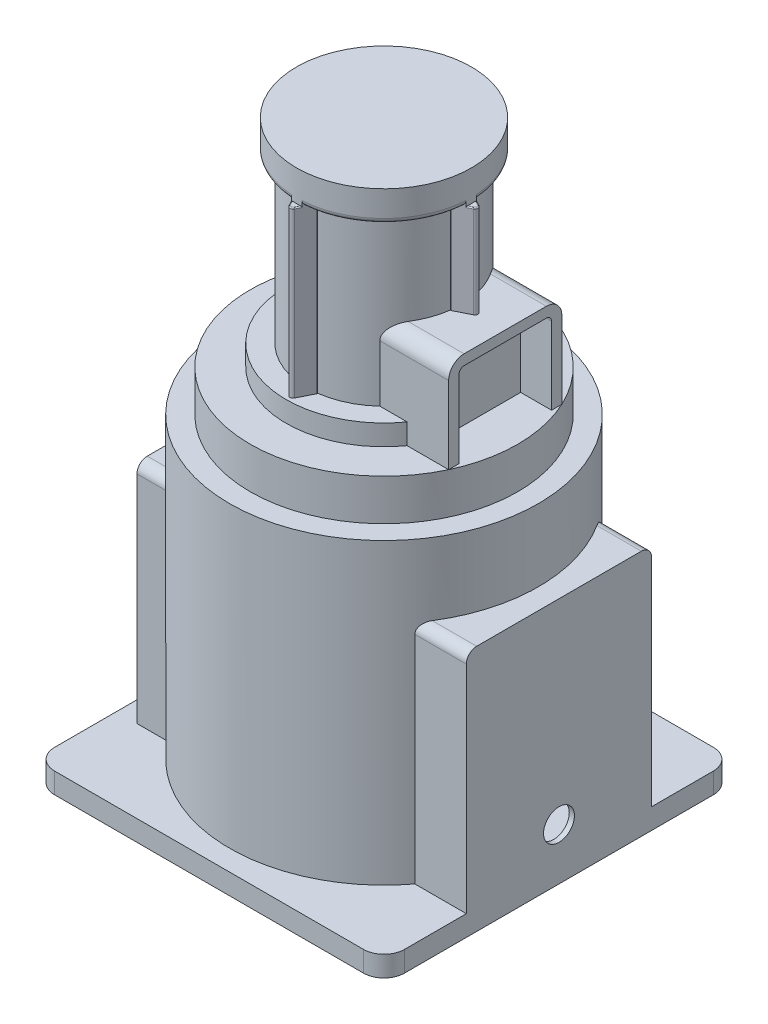
SolidWorks part; units mm, degrees
material "201 Annealed Stainless Steel (SS)"
ref_plane "Front Plane" through (0, 0, 0) normal (0, 0, 1) x (1, 0, 0)
ref_plane "Top Plane" through (0, 0, 0) normal (0, 1, 0) x (1, 0, 0)
ref_plane "Right Plane" through (0, 0, 0) normal (1, 0, 0) x (0, 0, -1)
sketch "Sketch1" plane through (0, 0, 0) normal (0, 1, 0) x (1, 0, 0)
  line L1 (150, -170) -> (-150, -170)
  line L2 (170, -150) -> (170, 150)
  line L3 (150, 170) -> (-150, 170)
  line L4 (-170, -150) -> (-170, 150)
  line L5 (170, -170) -> (-170, 170) construction
  line L6 (170, 170) -> (-170, -170) construction
  arc A0 (170, -150) -> (150, -170) centre (150, -150) cw
  arc A1 (-170, -150) -> (-150, -170) centre (-150, -150) ccw
  arc A2 (150, 170) -> (170, 150) centre (150, 150) cw
  arc A3 (-150, 170) -> (-170, 150) centre (-150, 150) ccw
  point P0 (0, 0)
  dimension "D3" = 20
  dimension "D1" = 340
  dimension "D2" = 340
extrude "Boss-Extrude1" add sketch "Sketch1" along normal blind 20
sketch "Sketch2" plane through (0, 20, 0) normal (0, 1, 0) x (1, 0, 0)
  line L4 (170, -150) -> (170, 150)
  line L5 (150, 170) -> (-150, 170)
  line L6 (-170, 150) -> (-170, -150)
  line L7 (-150, -170) -> (150, -170)
  line L8 (170, -150) -> (170, 150)
  line L9 (150, 170) -> (-150, 170)
  line L10 (-170, 150) -> (-170, -150)
  line L11 (-150, -170) -> (150, -170)
  line L12 (-150, 0) -> (-150, -90)
  line L13 (-150, -90) -> (-120, -90)
  line L14 (120, -90) -> (150, -90)
  line L15 (0, 0) -> (-150, 0) construction
  line L16 (150, -150) -> (150, 150)
  line L17 (150, 150) -> (-150, 150)
  line L18 (-150, 150) -> (-150, -150)
  line L19 (-150, -150) -> (150, -150)
  line L20 (150, -150) -> (150, 150)
  line L21 (150, 150) -> (-150, 150)
  line L22 (-150, 150) -> (-150, -150)
  line L23 (-150, -150) -> (150, -150)
  line L24 (150, -90) -> (170, -90)
  line L25 (150, 90) -> (170, 90)
  line L26 (120, 90) -> (150, 90)
  line L27 (-150, 90) -> (-120, 90)
  arc A4 (150, -170) -> (170, -150) centre (150, -150) ccw
  arc A5 (170, 150) -> (150, 170) centre (150, 150) ccw
  arc A6 (-150, 170) -> (-170, 150) centre (-150, 150) ccw
  arc A7 (-170, -150) -> (-150, -170) centre (-150, -150) ccw
  arc A8 (150, -170) -> (170, -150) centre (150, -150) ccw
  arc A9 (170, 150) -> (150, 170) centre (150, 150) ccw
  arc A10 (-150, 170) -> (-170, 150) centre (-150, 150) ccw
  arc A11 (-170, -150) -> (-150, -170) centre (-150, -150) ccw
  circle A12 centre (0, 0) radius 150
  dimension "D3" = 30
  dimension "D1" = 0
  dimension "D2" = 20
extrude "Boss-Extrude2" add sketch "Sketch2" along normal blind 220 contours A12 | A12 L12 L13 | A12 L14 L20 | L25 L20 L24 L8 | A12 L20 L26 | A12 L27 L22 region at (160, 20, 0) region at (141.1785, 20, 67.9748) region at (141.1785, 20, -67.9748) region at (0, 20, 0) region at (-141.1785, 20, 67.9748) region at (-141.1785, 20, -67.9748)
sketch "Sketch3" plane through (0, 240, 0) normal (0, 1, 0) x (1, 0, 0)
  line L6 (170, -90) -> (170, 90)
  line L7 (170, 90) -> (120, 90)
  line L8 (-120, 90) -> (-150, 90)
  line L9 (-150, 90) -> (-150, -90)
  line L10 (-150, -90) -> (-120, -90)
  line L11 (120, -90) -> (170, -90)
  line L12 (170, -90) -> (170, 90)
  line L13 (170, 90) -> (120, 90)
  line L14 (-120, 90) -> (-150, 90)
  line L15 (-150, 90) -> (-150, -90)
  line L16 (-150, -90) -> (-120, -90)
  line L17 (120, -90) -> (170, -90)
  circle A0 centre (0, 0) radius 150
  arc A2 (120, 90) -> (-120, 90) centre (0, 0) ccw
  arc A3 (-120, -90) -> (120, -90) centre (0, 0) ccw
  arc A4 (120, 90) -> (-120, 90) centre (0, 0) ccw
  arc A5 (-120, -90) -> (120, -90) centre (0, 0) ccw
  arc M11 (120, 90) -> (-120, 90) centre (0, 0) ccw
  arc M15 (-120, -90) -> (120, -90) centre (0, 0) ccw
  dimension "D1" = 0
extrude "Boss-Extrude3" add sketch "Sketch3" along normal blind 70 contours A0 M15 M11 region at (0, 240, 0)
sketch "Sketch4" plane through (0, 310, 0) normal (0, 1, 0) x (1, 0, 0)
  circle A1 centre (0, 0) radius 150
  circle A2 centre (0, 0) radius 150
  circle A4 centre (0, 0) radius 130
  circle A5 centre (0, 0) radius 130
  dimension "D1" = 0
  dimension "D2" = 20
extrude "Boss-Extrude4" add sketch "Sketch4" along normal blind 40 contours A5 region at (0, 310, 0)
sketch "Sketch5" plane through (0, 350, 0) normal (0, 1, 0) x (1, 0, 0)
  circle A1 centre (0, 0) radius 130
  circle A2 centre (0, 0) radius 130
  circle A4 centre (0, 0) radius 95
  circle A5 centre (0, 0) radius 95
  dimension "D1" = 0
  dimension "D2" = 35
extrude "Boss-Extrude5" add sketch "Sketch5" along normal blind 20 contours A5 region at (0, 350, 0)
sketch "Sketch6" plane through (0, 350, 0) normal (0, 1, 0) x (1, 0, 0)
  line L0 (0, 0) -> (0, -130) construction
  line L1 (0, 0) -> (0, -55)
  line L2 (0, -55) -> (117.7922, -55)
  line L3 (0, 0) -> (130, 0) construction
  line L4 (0, 55) -> (117.7922, 55)
  line L5 (0, 0) -> (0, 55)
  line L6 (117.7922, 55) -> (117.7922, -55)
  circle A1 centre (0, 0) radius 130
  circle A2 centre (0, 0) radius 130
  circle M5 centre (0, 0) radius 95
  dimension "D2" = 55
  dimension "D1" = 0
extrude "Boss-Extrude6" add sketch "Sketch6" along normal blind 90 contours L5 L1 L2 L4 M5 | L6 L4 L2 M5 region at (44.8421, 350, 0) region at (103.1235, 350, 0)
sketch "Sketch7" plane through (0, 370, 0) normal (0, 1, 0) x (1, 0, 0)
  line L3 (77.4597, -55) -> (0, -55)
  line L4 (0, -55) -> (0, 55)
  line L5 (0, 55) -> (77.4597, 55)
  line L6 (77.4597, -55) -> (0, -55)
  line L7 (0, -55) -> (0, 55)
  line L8 (0, 55) -> (77.4597, 55)
  line L9 (0, 0) -> (-95, 0) construction
  line L10 (-75, 0) -> (-75, 10)
  line L11 (-75, 10) -> (-89.6334, 2.6833)
  line L12 (-20, -72.2842) -> (-20, 72.2842)
  line L13 (-20, -72.2842) -> (-20, 72.2842)
  line L14 (-75, 10) -> (-74.3421, 9.9123)
  line L15 (-75, -10) -> (-74.3421, -9.9123)
  line L16 (-75, -10) -> (-89.6334, -2.6833)
  line L17 (10, 75) -> (2.6833, 89.6334)
  line L18 (-10, 75) -> (-2.6833, 89.6334)
  line L19 (10, 75) -> (9.9123, 74.3421)
  line L20 (-10, 75) -> (-9.9123, 74.3421)
  line L21 (75, -10) -> (89.6334, -2.6833)
  line L22 (75, 10) -> (89.6334, 2.6833)
  line L23 (75, -10) -> (74.3421, -9.9123)
  line L24 (75, 10) -> (74.3421, 9.9123)
  line L25 (-10, -75) -> (-2.6833, -89.6334)
  line L26 (10, -75) -> (2.6833, -89.6334)
  line L27 (-10, -75) -> (-9.9123, -74.3421)
  line L28 (10, -75) -> (9.9123, -74.3421)
  arc A1 (77.4597, 55) -> (77.4597, -55) centre (0, 0) ccw
  arc A2 (77.4597, 55) -> (77.4597, -55) centre (0, 0) ccw
  circle A3 centre (0, 0) radius 75
  arc A4 (-20, 72.2842) -> (-20, -72.2842) centre (0, 0) ccw
  arc A5 (-20, 72.2842) -> (-20, -72.2842) centre (0, 0) ccw
  arc A6 (-89.6334, -2.6833) -> (-89.6334, 2.6833) centre (-88.2918, 0) cw
  arc A7 (-2.6833, 89.6334) -> (2.6833, 89.6334) centre (0, 88.2918) cw
  arc A8 (89.6334, 2.6833) -> (89.6334, -2.6833) centre (88.2918, 0) cw
  arc A9 (2.6833, -89.6334) -> (-2.6833, -89.6334) centre (0, -88.2918) cw
  line M9 (0, -55) -> (0, 55)
  line M10 (0, 55) -> (77.4597, 55)
  dimension "D1" = 0
  dimension "D2" = 20
extrude "Boss-Extrude7" add sketch "Sketch7" along normal blind 160 contours L13 L9 A3 | L9 L13 A3 | A3 L9 A6 L16 L15 | L9 L10 L11 A6 | A7 L18 L20 A3 L19 L17 | A8 L22 L24 A3 L23 L21 | A9 L26 L28 A3 L27 L25 | L9 L13 A3 L6 M9 | L9 L7 A3 L13 M10 | L6 A3 L7 M10 M9 region at (-0.4873, 370, 45.4129) region at (34.1514, 370, 0) region at (0, 370, 81.0778) region at (81.0778, 370, 0) region at (-81.2216, 370, -3.4408) region at (-81.0778, 370, 3.5311) region at (-0.4873, 370, -45.4129) region at (-42.8821, 370, -29.1938) region at (-42.8821, 370, 29.1938) region at (0, 370, -81.0778)
sketch "Sketch8" plane through (0, 530, 0) normal (0, 1, 0) x (1, 0, 0)
  line L16 (-75, 0) -> (-75, 10)
  line L17 (-75, 10) -> (-89.6334, 2.6833)
  line L18 (-89.6334, -2.6833) -> (-75, -10)
  line L19 (-75, -10) -> (-74.3421, -9.9123)
  line L20 (-9.9123, -74.3421) -> (-10, -75)
  line L21 (-10, -75) -> (-2.6833, -89.6334)
  line L22 (2.6833, -89.6334) -> (10, -75)
  line L23 (10, -75) -> (9.9123, -74.3421)
  line L24 (74.3421, -9.9123) -> (75, -10)
  line L25 (75, -10) -> (89.6334, -2.6833)
  line L26 (89.6334, 2.6833) -> (75, 10)
  line L27 (75, 10) -> (74.3421, 9.9123)
  line L28 (9.9123, 74.3421) -> (10, 75)
  line L29 (10, 75) -> (2.6833, 89.6334)
  line L30 (-2.6833, 89.6334) -> (-10, 75)
  line L31 (-10, 75) -> (-9.9123, 74.3421)
  line L32 (-75, 0) -> (-75, 10)
  line L33 (-75, 10) -> (-89.6334, 2.6833)
  line L34 (-89.6334, -2.6833) -> (-75, -10)
  line L35 (-75, -10) -> (-74.3421, -9.9123)
  line L36 (-9.9123, -74.3421) -> (-10, -75)
  line L37 (-10, -75) -> (-2.6833, -89.6334)
  line L38 (2.6833, -89.6334) -> (10, -75)
  line L39 (10, -75) -> (9.9123, -74.3421)
  line L40 (74.3421, -9.9123) -> (75, -10)
  line L41 (75, -10) -> (89.6334, -2.6833)
  line L42 (89.6334, 2.6833) -> (75, 10)
  line L43 (75, 10) -> (74.3421, 9.9123)
  line L44 (9.9123, 74.3421) -> (10, 75)
  line L45 (10, 75) -> (2.6833, 89.6334)
  line L46 (-2.6833, 89.6334) -> (-10, 75)
  line L47 (-10, 75) -> (-9.9123, 74.3421)
  arc A0 (-11.2339, 84.2544) -> (-85, 0) centre (0, 0) ccw
  circle A1 centre (0, 0) radius 85
  arc A8 (-9.9123, 74.3421) -> (-75, 0) centre (0, 0) ccw
  arc A9 (-89.6334, 2.6833) -> (-89.6334, -2.6833) centre (-88.2918, 0) ccw
  arc A10 (-74.3421, -9.9123) -> (-9.9123, -74.3421) centre (0, 0) ccw
  arc A11 (-2.6833, -89.6334) -> (2.6833, -89.6334) centre (0, -88.2918) ccw
  arc A12 (9.9123, -74.3421) -> (74.3421, -9.9123) centre (0, 0) ccw
  arc A13 (89.6334, -2.6833) -> (89.6334, 2.6833) centre (88.2918, 0) ccw
  arc A14 (74.3421, 9.9123) -> (9.9123, 74.3421) centre (0, 0) ccw
  arc A15 (2.6833, 89.6334) -> (-2.6833, 89.6334) centre (0, 88.2918) ccw
  arc A16 (-9.9123, 74.3421) -> (-75, 0) centre (0, 0) ccw
  arc A17 (-89.6334, 2.6833) -> (-89.6334, -2.6833) centre (-88.2918, 0) ccw
  arc A18 (-74.3421, -9.9123) -> (-9.9123, -74.3421) centre (0, 0) ccw
  arc A19 (-2.6833, -89.6334) -> (2.6833, -89.6334) centre (0, -88.2918) ccw
  arc A20 (9.9123, -74.3421) -> (74.3421, -9.9123) centre (0, 0) ccw
  arc A21 (89.6334, -2.6833) -> (89.6334, 2.6833) centre (88.2918, 0) ccw
  arc A22 (74.3421, 9.9123) -> (9.9123, 74.3421) centre (0, 0) ccw
  arc A23 (2.6833, 89.6334) -> (-2.6833, 89.6334) centre (0, 88.2918) ccw
  arc M25 (-9.9123, 74.3421) -> (-75, 0) centre (0, 0) ccw
  line M26 (-75, 0) -> (-75, 10)
  line M27 (-75, 10) -> (-89.6334, 2.6833)
  line M30 (-75, -10) -> (-74.3421, -9.9123)
  arc M31 (-74.3421, -9.9123) -> (-9.9123, -74.3421) centre (0, 0) ccw
  line M32 (-9.9123, -74.3421) -> (-10, -75)
  line M33 (-10, -75) -> (-2.6833, -89.6334)
  line M36 (10, -75) -> (9.9123, -74.3421)
  arc M37 (9.9123, -74.3421) -> (74.3421, -9.9123) centre (0, 0) ccw
  line M38 (74.3421, -9.9123) -> (75, -10)
  line M39 (75, -10) -> (89.6334, -2.6833)
  line M42 (75, 10) -> (74.3421, 9.9123)
  arc M43 (74.3421, 9.9123) -> (9.9123, 74.3421) centre (0, 0) ccw
  line M44 (9.9123, 74.3421) -> (10, 75)
  line M45 (10, 75) -> (2.6833, 89.6334)
  line M48 (-10, 75) -> (-9.9123, 74.3421)
  dimension "D1" = 0
  dimension "D2" = 10
extrude "Boss-Extrude8" add sketch "Sketch8" along normal blind 30 contours A1 L42 L46 A0 L34 L38 M39 M42 M43 M44 M45 M48 M25 M26 M27 M30 M31 M32 M33 M36 M37 M38 | A1 region at (0.009, 530, 0.0009)
fillet "Fillet1" radius 10 4 edges at (-135, 240, 90) (-135, 240, -90) (145, 240, -90) (145, 240, 90)
fillet "Fillet2" radius 15 2 edges at (84.3912, 440, -55) (84.3912, 440, 55)
fillet "Fillet3" radius 5 4 edges at (60.1041, 530, 60.1041) (60.1041, 530, -60.1041) (-60.1041, 530, -60.1041) (-60.1041, 530, 60.1041)
fillet "Fillet4" radius 1 12 edges at (-3.8796, 530, 87.2409) (0, 530, 91.2918) (87.2409, 530, 3.8796) (91.2918, 530, 0) (3.8796, 530, -87.2409) (0, 530, -91.2918) (-87.2409, 530, 3.8796) (-91.2918, 530, 0) (3.8796, 530, 87.2409) (87.2409, 530, -3.8796) (-3.8796, 530, -87.2409) (-87.2409, 530, -3.8796)
sketch "Sketch10" plane through (170, 0, 0) normal (1, 0, 0) x (0, 0, -1)
  line L0 (80, 20) -> (80, 220)
  line L1 (70, 230) -> (-70, 230)
  line L2 (-80, 220) -> (-80, 20)
  line L3 (80, 20) -> (80, 230) construction
  line L4 (80, 230) -> (-80, 230) construction
  line L5 (-80, 230) -> (-80, 20) construction
  line L6 (80, 20) -> (-80, 20)
  line L8 (90, 20) -> (90, 230)
  line L9 (80, 240) -> (-80, 240)
  line L10 (-90, 230) -> (-90, 20)
  line L11 (-90, 20) -> (-150, 20)
  line L12 (-150, 20) -> (-150, 0)
  line L13 (-150, 0) -> (150, 0)
  line L14 (150, 0) -> (150, 20)
  line L15 (150, 20) -> (90, 20)
  line L16 (90, 20) -> (90, 230)
  line L17 (80, 240) -> (-80, 240)
  line L18 (-90, 230) -> (-90, 20)
  line L19 (-90, 20) -> (-150, 20)
  line L20 (-150, 20) -> (-150, 0)
  line L21 (-150, 0) -> (150, 0)
  line L22 (150, 0) -> (150, 20)
  line L23 (150, 20) -> (90, 20)
  arc A0 (-80, 220) -> (-70, 230) centre (-70, 220) cw
  arc A2 (90, 230) -> (80, 240) centre (80, 230) ccw
  arc A3 (-80, 240) -> (-90, 230) centre (-80, 230) ccw
  arc A4 (90, 230) -> (80, 240) centre (80, 230) ccw
  arc A5 (-80, 240) -> (-90, 230) centre (-80, 230) ccw
  arc A6 (80, 220) -> (70, 230) centre (70, 220) ccw
  arc A7 (80, 230) -> (80, 230) centre (80, 230) ccw construction
  arc A8 (-80, 230) -> (-80, 230) centre (-80, 230) ccw construction
  dimension "D3" = 10
  dimension "D1" = 0
  dimension "D2" = 10
extrude "Cut-Extrude1" cut sketch "Sketch10" against normal up to surface (320 mm away) contours L0 A6 L1 A0 L2 L6 region at (170, 124.8686, 0) up to face at (-150, 174.8774, 0)
sketch "Sketch11" plane through (117.7922, 0, 0) normal (1, 0, 0) x (0, 0, -1)
  line L0 (45, 350) -> (45, 425)
  line L1 (40, 430) -> (-40, 430)
  line L2 (-45, 425) -> (-45, 350)
  line L4 (55, 350) -> (55, 425)
  line L5 (40, 440) -> (-40, 440)
  line L6 (-55, 425) -> (-55, 350)
  line L7 (-55, 350) -> (55, 350)
  line L8 (55, 350) -> (55, 425)
  line L9 (40, 440) -> (-40, 440)
  line L10 (-55, 425) -> (-55, 350)
  line L11 (-55, 350) -> (55, 350)
  arc A0 (45, 425) -> (40, 430) centre (40, 425) ccw
  arc A1 (-40, 430) -> (-45, 425) centre (-40, 425) ccw
  arc A2 (55, 425) -> (40, 440) centre (40, 425) ccw
  arc A3 (-40, 440) -> (-55, 425) centre (-40, 425) ccw
  arc A4 (55, 425) -> (40, 440) centre (40, 425) ccw
  arc A5 (-40, 440) -> (-55, 425) centre (-40, 425) ccw
  line M12 (-55, 350) -> (55, 350)
  dimension "D1" = 0
  dimension "D2" = 10
extrude "Cut-Extrude3" cut sketch "Sketch11" against normal blind 30 contours L1 A1 L2 L0 A0 M12 region at (117.7922, 389.942, 0)
sketch "Sketch14" plane through (0, 20, 0) normal (0, 1, 0) x (1, 0, 0)
  line L0 (170, -80) -> (165, -80)
  line L1 (165, -80) -> (165, 80)
  line L14 (170, -90) -> (120, -90)
  line L15 (-120, -90) -> (-150, -90)
  line L16 (-150, -90) -> (-150, -80)
  line L17 (-150, -80) -> (170, -80)
  line L18 (170, -80) -> (170, 80)
  line L19 (170, 80) -> (-150, 80)
  line L20 (-150, 80) -> (-150, 90)
  line L21 (-150, 90) -> (-120, 90)
  line L22 (120, 90) -> (170, 90)
  line L23 (170, 90) -> (170, 150)
  line L24 (150, 170) -> (-150, 170)
  line L25 (-170, 150) -> (-170, -150)
  line L26 (-150, -170) -> (150, -170)
  line L27 (170, -150) -> (170, -90)
  line L28 (170, -90) -> (120, -90)
  line L29 (-120, -90) -> (-150, -90)
  line L30 (-150, -90) -> (-150, -80)
  line L31 (-150, -80) -> (170, -80)
  line L32 (170, -80) -> (170, 80)
  line L33 (170, 80) -> (-150, 80)
  line L34 (-150, 80) -> (-150, 90)
  line L35 (-150, 90) -> (-120, 90)
  line L36 (120, 90) -> (170, 90)
  line L37 (170, 90) -> (170, 150)
  line L38 (150, 170) -> (-150, 170)
  line L39 (-170, 150) -> (-170, -150)
  line L40 (-150, -170) -> (150, -170)
  line L41 (170, -150) -> (170, -90)
  arc A6 (-120, -90) -> (120, -90) centre (0, 0) ccw
  arc A7 (120, 90) -> (-120, 90) centre (0, 0) ccw
  arc A8 (170, 150) -> (150, 170) centre (150, 150) ccw
  arc A9 (-150, 170) -> (-170, 150) centre (-150, 150) ccw
  arc A10 (-170, -150) -> (-150, -170) centre (-150, -150) ccw
  arc A11 (150, -170) -> (170, -150) centre (150, -150) ccw
  arc A12 (-120, -90) -> (120, -90) centre (0, 0) ccw
  arc A13 (120, 90) -> (-120, 90) centre (0, 0) ccw
  arc A14 (170, 150) -> (150, 170) centre (150, 150) ccw
  arc A15 (-150, 170) -> (-170, 150) centre (-150, 150) ccw
  arc A16 (-170, -150) -> (-150, -170) centre (-150, -150) ccw
  arc A17 (150, -170) -> (170, -150) centre (150, -150) ccw
  line M26 (-150, -80) -> (170, -80)
  line M27 (170, -80) -> (170, 80)
  line M28 (170, 80) -> (-150, 80)
  dimension "D2" = 5
  dimension "D1" = 0
extrude "Boss-Extrude9" add sketch "Sketch14" along normal up to surface (210 mm away) contours L1 M26 M27 M28 region at (167.5, 20, 0) up to face at (10, 230, 0)
sketch "Sketch15" plane through (170, 0, 0) normal (1, 0, 0) x (0, 0, -1)
  line L0 (0, 0) -> (0, 50)
  line L1 (-150, 0) -> (150, 0) construction
  circle A0 centre (0, 50) radius 15
  dimension "D1" = 50
extrude "Cut-Extrude4" cut sketch "Sketch15" against normal up to surface (5 mm away) contours A0 region at (170, 39.6934, -10.3066) up to face at (165, 157.357, 0)
